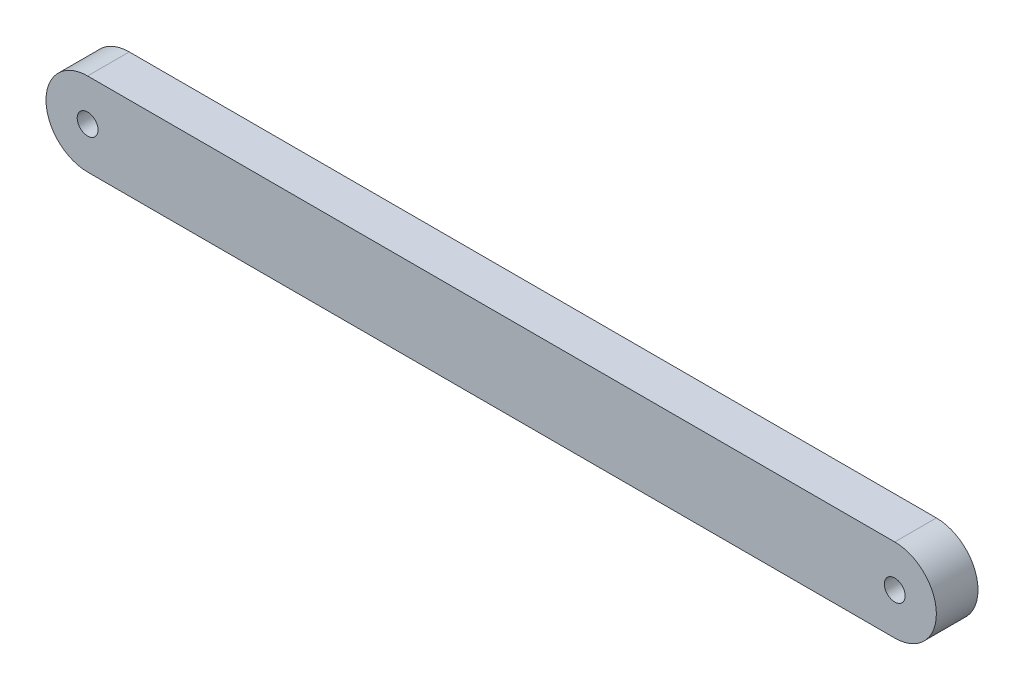
SolidWorks part; units mm, degrees
material "Nylon 101"
ref_plane "Front Plane" through (0, 0, 0) normal (0, 0, 1) x (1, 0, 0)
ref_plane "Top Plane" through (0, 0, 0) normal (0, 1, 0) x (1, 0, 0)
ref_plane "Right Plane" through (0, 0, 0) normal (1, 0, 0) x (0, 0, -1)
sketch "Sketch1" plane through (0, 0, 0) normal (0, 0, 1) x (1, 0, 0)
  line L1 (-53.4667, 5) -> (53.4668, 5)
  line L2 (-53.4667, 5) -> (-53.4667, -5)
  line L3 (-53.4667, -5) -> (53.4668, -5)
  line L4 (53.4668, 5) -> (53.4668, -5)
  line L5 (-53.4667, 5) -> (53.4668, -5) construction
  line L6 (-53.4667, -5) -> (53.4668, 5) construction
  point P0 (0, 0)
  point P5 (0, 0)
  dimension "D1" = 10
  dimension "D2" = 106.9335
extrude "Boss-Extrude1" add sketch "Sketch1" along normal blind 5
fillet "Fillet1" 2 edges at (-53.4667, 5, 2.5) (-53.4667, -5, 2.5) type full round first side face at (0, 5, 2.5) second side face at (0, -5, 2.5) middle face at (-53.4667, 0, 2.5)
fillet "Fillet2" 2 edges at (53.4668, 5, 2.5) (53.4668, -5, 2.5) type full round first side face at (2.5, 5, 2.5) second side face at (2.5, -5, 2.5) middle face at (53.4668, 0, 2.5)
hole_wizard "M3x0.5 Tapped Hole1" positions "Sketch2" profile "Sketch3" tap size "M3x0.5" standard "ANSI Metric"
sketch "Sketch2" plane through (0, 0, 5) normal (0, 0, 1) x (1, 0, 0)
  arc A1 (48.4668, -5) -> (48.4668, 5) centre (48.4668, 0) ccw construction
  point P0 (-48.4667, 0)
  point P2 (48.4668, 0)
  point P5 (0, 0)
  point P9 (0, 0)
  point P13 (0, 0)
  point P14 (0, 0)
  dimension "D1" = 96.9335
sketch "Sketch3" plane through (-48.4667, 0, 5) normal (1, 0, 0) x (0, -1, 0)
  line L0 (0, 0) -> (0, 30.5611)
  line L1 (0, 30.5611) -> (1.25, 29.81)
  line L2 (1.25, 29.81) -> (1.25, 0)
  line L5 (1.25, 0) -> (0, 0)
  line L10 (0, 30.5611) -> (-1.25, 29.81) construction
  line L11 (0, -6.35) -> (0, 107.95) construction
  dimension "Tap Drill Dia." = 2.5
  dimension "Tap Drill Depth" = 29.81
  dimension "Drill Angle" = 118
cosmetic thread "Hole Thread1" parameters "D1"=28.31, "D2"=3
cosmetic thread "Hole Thread3" parameters "D1"=28.31, "D2"=3
